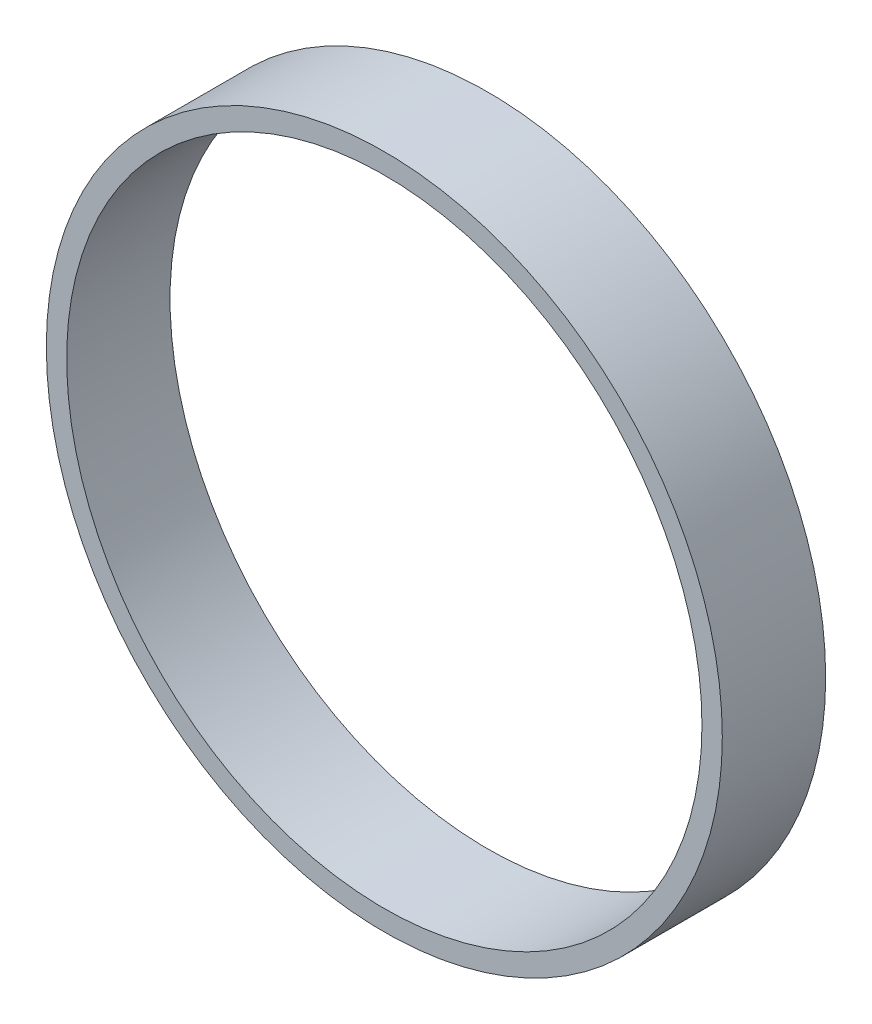
SolidWorks part; units mm, degrees
ref_plane "Front Plane" through (0, 0, 0) normal (0, 0, 1) x (1, 0, 0)
ref_plane "Top Plane" through (0, 0, 0) normal (0, 1, 0) x (1, 0, 0)
ref_plane "Right Plane" through (0, 0, 0) normal (1, 0, 0) x (0, 0, -1)
sketch "Sketch1" plane through (0, 0, 0) normal (0, 0, 1) x (1, 0, 0)
  circle A0 centre (0, 0) radius 78.05
  circle A1 centre (0, 0) radius 83.05
  dimension "Out_dia" = 166.1
  dimension "Thickness" = 5
extrude "BasePipe" add sketch "Sketch1" along normal mid plane 25.4
